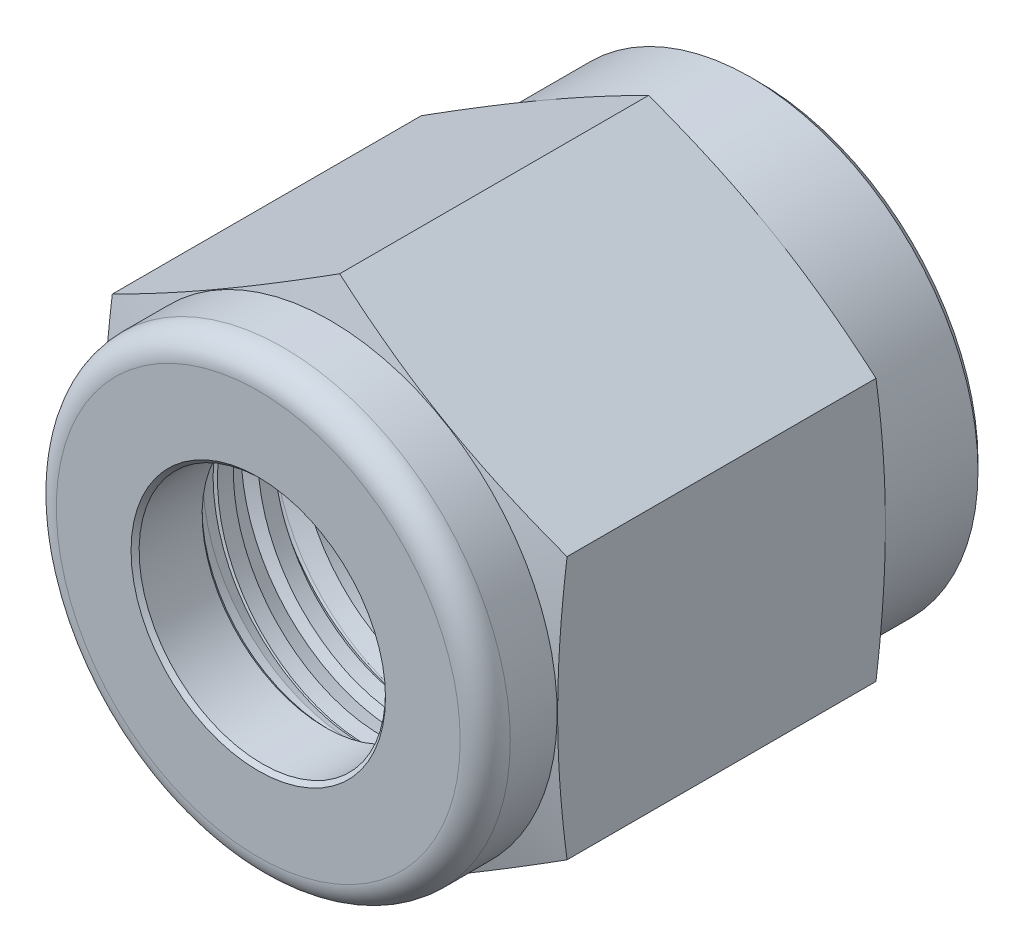
SolidWorks part; units mm, degrees
note: '?' marks a value the reader was unsure of.
ref_plane "Front Plane" through (0, 0, 0) normal (0, 0, 1) x (1, 0, 0)
ref_plane "Top Plane" through (0, 0, 0) normal (0, 1, 0) x (1, 0, 0)
ref_plane "Right Plane" through (0, 0, 0) normal (1, 0, 0) x (0, 0, -1)
sketch "Sketch0" plane through (0, 0, 0) normal (1, 0, 0) x (0, 0, -1)
  line L0 (0, 0) -> (-15.748, 0) construction
  line L4 (-15.748, 7.1501) -> (-15.748, -7.1501) construction
  line L5 (-15.748, 7.1374) -> (-15.748, -7.1374) construction
  line L6 (-15.748, 3.8735) -> (-15.748, -3.8735) construction
  line L7 (0, 5.5562) -> (0, -5.5562) construction
  line L8 (0, -5.5626) -> (0, 5.5626) construction
  line L9 (0, -5.5626) -> (-1.27, -5.5626) construction
  point P16 (-13.5128, 0)
  point P20 (-12.7, 0)
  point P22 (-9.652, 0)
  point P34 (-3.175, 0)
  point P35 (-13.4874, 0)
  dimension "P" = 14.3002
  dimension "M" = 15.748
  dimension "L" = 13.5128
  dimension "S" = 12.7
  dimension "Q" = 9.652
  dimension "A" = 7.747
  dimension "C" = 14.2748
  dimension "T" = 11.1125
  dimension "B" = 3.175
  dimension "J" = 10.3124
  dimension "H" = 11.1252
  dimension "Pitch" = 1.27
sketch "Sketch1" plane through (0, 0, 0) normal (0, 0, 1) x (1, 0, 0)
  line L1 (0, 8.2562) -> (-7.1501, 4.1281)
  line L2 (-7.1501, 4.1281) -> (-7.1501, -4.1281)
  line L3 (-7.1501, -4.1281) -> (0, -8.2562)
  line L4 (0, -8.2562) -> (7.1501, -4.1281)
  line L5 (7.1501, -4.1281) -> (7.1501, 4.1281)
  line L6 (7.1501, 4.1281) -> (0, 8.2562)
  circle A0 centre (0, 0) radius 7.1501 construction
extrude "Boss-Extrude1" add sketch "Sketch1" along normal up to vertex (15.748 mm away) up to point (0, 0, 15.748)
sketch "Sketch2" plane through (0, 0, 0) normal (1, 0, 0) x (0, 0, -1)
  line L0 (-15.748, 9.375) -> (-15.748, 7.1374)
  line L1 (-15.748, 7.1374) -> (-13.4874, 7.1374)
  line L2 (-13.4874, 7.1374) -> (-13.1876, 8.2562)
  line L3 (-15.748, 8.2562) -> (0, 8.2562) construction
  line L4 (-13.1876, 8.2562) -> (-3.4748, 8.2562)
  line L5 (-3.4748, 8.2562) -> (-3.175, 7.1374)
  line L6 (-3.175, 7.1374) -> (-13.4874, 7.1374) construction
  line L7 (-3.175, 7.1374) -> (0, 7.1374)
  line L8 (0, 7.1374) -> (0, 9.375)
  line L9 (-15.748, 9.375) -> (0, 9.375)
  line L10 (-3.175, 7.1374) -> (-3.175, 0) construction
  line L11 (-13.4874, 7.1374) -> (-13.4874, 0) construction
  line L12 (-15.748, 3.8735) -> (-15.748, 0)
  line L13 (-15.748, 7.1501) -> (-15.748, -7.1501) construction
  line L14 (-15.748, 0) -> (0, 0)
  line L15 (0, 0) -> (0, 4.7829)
  line L16 (-13.5128, 3.8735) -> (-13.5128, 0) construction
  line L17 (-13.5128, 3.8735) -> (-13.5128, 4.5289)
  line L18 (-13.2588, 4.7829) -> (0, 4.7829)
  line L19 (-13.5128, 3.8735) -> (-15.748, 3.8735)
  line L23 (-12.7, 0) -> (-12.7, 4.7829) construction
  arc A0 (-13.5128, 4.5289) -> (-13.2588, 4.7829) centre (-13.2588, 4.5289) cw
  dimension "D3" = 0.254
  dimension "D1" = 15
  dimension "D2" = 15
  dimension "D4" = 0.7733
revolve "Cut-Revolve1" cut sketch "Sketch2" angle 360 about L0
sketch "Sketch3" plane through (0, 0, 0) normal (0, 0, -1) x (-1, 0, 0)
  circle A0 centre (0, 0) radius 4.7829
  circle A1 centre (0, 0) radius 4.7829 construction
  point P3 (0, 4.7829)
fillet "Fillet1" radius 0.7874 1 edges at (0, 7.1374, 15.748)
chamfer "Chamfer1" distance 0.254 angle 45 1 edges at (0, 7.1374, 0)
chamfer "Chamfer2" distance 0.127 angle 45 2 edges at (0, 3.8735, 13.5128) (0, 3.8735, 15.748)
ref_axis "Centre Axis 1" through (0, 0, 25.2505) along (0, 0, -1)?
curve "Helix/Spiral1" pitch 1.27 height 13.97 turns 11 parameters "Pitch"=1.27
sketch "Sketch4" plane through (0, 0, 0) normal (1, 0, 0) x (0, 0, -1)
  line L0 (-0.248, 4.3533) -> (1.022, 4.3533) construction
  line L1 (1.022, 4.3533) -> (0.387, 5.4531) construction
  line L2 (0.387, 5.4531) -> (-0.248, 4.3533) construction
  line L3 (0.2877, 5.2813) -> (0.4862, 5.2813) construction
  line L4 (0.387, 4.7829) -> (0.387, 4.3533) construction
  line L5 (0, 4.7829) -> (0.7739, 4.7829) construction
  line L6 (0.387, 5.4531) -> (0.387, 5.2813) construction
  line L7 (0.2877, 5.2813) -> (-0.124, 4.5681)
  line L8 (-0.124, 4.5681) -> (0.8979, 4.5681)
  line L9 (0.8979, 4.5681) -> (0.4862, 5.2813)
  arc A0 (0.4862, 5.2813) -> (0.2877, 5.2813) centre (0.387, 5.224) ccw
  point P6 (0.387, 4.5681)
  dimension "D1" = 1.27
  dimension "D2" = 1.0999
  dimension "D4" = 0.4296
  dimension "D3" = 0.1719
  dimension "D5" = 0.4984
sweep "Cut-Sweep1" cut profiles "Sketch4" path "Helix/Spiral1" align with end faces yes
sketch "Sketch5" plane through (0, 0, 0) normal (0, 0, -1) x (-1, 0, 0)
  circle A0 centre (0, 0) radius 5.5626
extrude "Cut-Extrude1" cut sketch "Sketch5" against normal through all draft 45
sketch "Sketch6" plane through (0, 0, 0) normal (1, 0, 0) x (0, 0, -1)
  line L0 (-13.5128, 5.4531) -> (-9.652, 5.4531)
  line L1 (-9.652, 5.4531) -> (-12.7, 4.7829)
  line L2 (-12.7, 4.7829) -> (-13.5128, 4.7829)
  line L3 (-13.5128, 4.7829) -> (-13.5128, 5.4531)
  line L4 (-9.652, 0) -> (-9.652, 5.4531) construction
  line L5 (-12.7, 0) -> (-12.7, 4.7829) construction
  line L7 (-13.5128, 4.7829) -> (-13.5128, 0) construction
  line L8 (-13.2588, 4.7829) -> (0, 4.7829) construction
  line L9 (-9.652, 5.4531) -> (0.387, 5.4531) construction
revolve "Revolve1" add sketch "Sketch6" angle 360 about L0
sketch "SketchX" plane through (0, 0, 0) normal (0, 0, -1) x (-1, 0, 0)
  line L0 (0, 0) -> (-2.7813, 4.8174) construction
  line L1 (0, 8.2562) -> (-7.1501, 4.1281) construction
  circle A0 centre (0, 0) radius 5.5626 construction
equation "\"D3@Helix/Spiral1\"= \"Pitch@Sketch0\" + \"S@Sketch0\""
equation "\"D1@Sketch4\"=\"Pitch@Sketch0\""
equation "\"Pitch@Helix/Spiral1\"=\"Pitch@Sketch0\""
